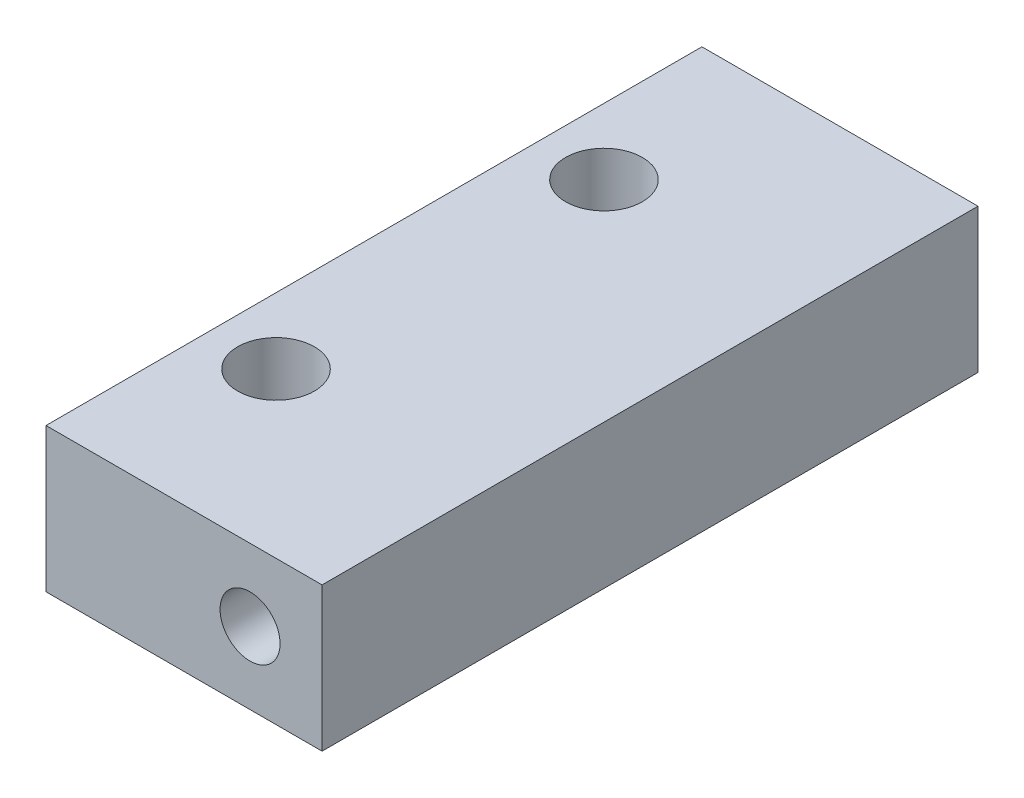
SolidWorks part; units mm, degrees
ref_plane "Front" through (0, 0, 0) normal (0, 0, 1) x (1, 0, 0)
ref_plane "Top" through (0, 0, 0) normal (0, 1, 0) x (1, 0, 0)
ref_plane "Right" through (0, 0, 0) normal (1, 0, 0) x (0, 0, -1)
sketch "Sketch1" plane through (0, 0, 0) normal (0, 1, 0) x (1, 0, 0)
  line L0 (0, 27.323) -> (5.5, 27.323)
  line L1 (0, 0) -> (11.5, 0)
  line L2 (0, 0) -> (0, 27.323)
  line L3 (0, 27.323) -> (11.5, 27.323)
  line L4 (11.5, 0) -> (11.5, 27.323)
  line L5 (2.75, 27.323) -> (2.75, 0)
  line L6 (2.75, 13.6615) -> (2.75, 20.492)
  line L7 (2.75, 13.6615) -> (2.75, 6.831)
  circle A0 centre (2.75, 20.492) radius 1.6
  circle A1 centre (2.75, 6.831) radius 1.6
  dimension "D1" = 27.323
  dimension "D2" = 11.5
  dimension "D3" = 5.5
  dimension "D4" = 6.8305
  dimension "D5" = 6.8305
extrude "Boss-Extrude1" add sketch "Sketch1" along normal blind 6 contours A1 L5 L1 L4 L3 A0 L6 | A1 L5 L6 A0 L0 L2 L1 region at (1.2916, 0, -13.6615) region at (7.2537, 0, -13.6615)
sketch "Sketch2" plane through (0, 0, 0) normal (0, 0, 1) x (1, 0, 0)
  line L0 (11.5, 6) -> (5.5, 6)
  line L1 (0, 6) -> (11.5, 6) construction
  line L2 (8.5, 6) -> (8.5, 0)
  line L3 (0, 0) -> (11.5, 0) construction
  circle A0 centre (8.5, 3) radius 1.25
  dimension "D1" = 6
extrude "Cut-Extrude1" cut sketch "Sketch2" against normal through all contours A0
